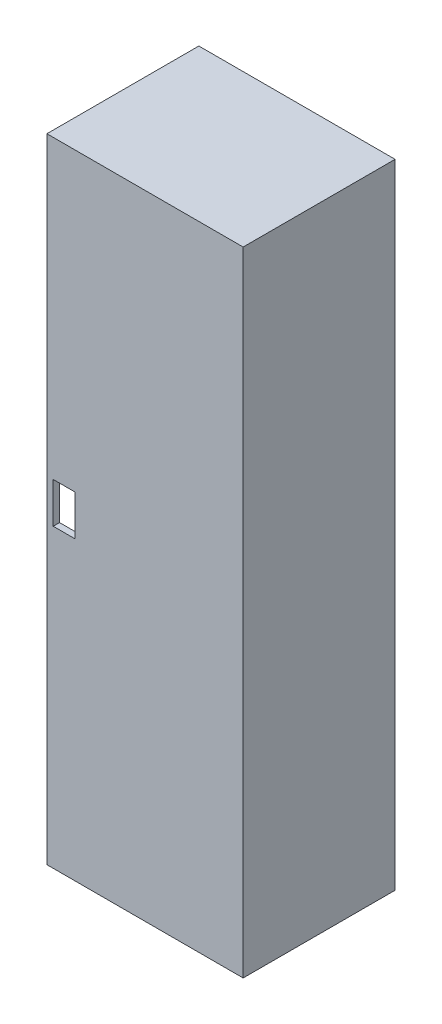
SolidWorks part; units mm, degrees
material "PLA"
ref_plane "Front Plane" through (0, 0, 0) normal (1, 0, 0) x (0, 1, 0)
ref_plane "Top Plane" through (0, 0, 0) normal (0, 0, 1) x (0, 1, 0)
ref_plane "Right Plane" through (0, 0, 0) normal (0, 1, 0) x (-1, 0, 0)
sketch "Sketch1" plane through (0, 0, 0) normal (0, 0, 1) x (0, 1, 0)
  line L1 (-125, -40) -> (125, -40)
  line L2 (-125, -40) -> (-125, 40)
  line L3 (-125, 40) -> (125, 40)
  line L4 (125, -40) -> (125, 40)
  line L5 (-125, -40) -> (125, 40) construction
  line L6 (-125, 40) -> (125, -40) construction
  point P0 (0, 0)
  dimension "D1" = 250
extrude "Boss-Extrude1" add sketch "Sketch1" along normal blind 2.5
sketch "Sketch2" plane through (0, 0, 0) normal (0, 0, -1) x (1, 0, 0)
  line L1 (-40, 125) -> (40, 125) construction
  line L2 (-37.5, -122.5) -> (37.5, -122.5)
  line L3 (-37.5, -122.5) -> (-37.5, 122.5)
  line L4 (-40, -125) -> (40, -125)
  line L5 (40, -125) -> (40, 125)
  line L6 (40, 125) -> (-40, 125)
  line L7 (-40, 125) -> (-40, -125)
  line L8 (-40, -125) -> (40, -125)
  line L9 (40, -125) -> (40, 125)
  line L10 (40, 125) -> (-40, 125)
  line L11 (-40, 125) -> (-40, -125)
  line L12 (-37.5, 122.5) -> (37.5, 122.5)
  line L13 (37.5, -122.5) -> (37.5, 122.5)
  line L14 (-37.5, -122.5) -> (37.5, 122.5) construction
  line L15 (-37.5, 122.5) -> (37.5, -122.5) construction
  point P2 (0, 0)
  dimension "D2" = 2.5
  dimension "D3" = 2.5
extrude "Boss-Extrude2" add sketch "Sketch2" along normal blind 55
sketch "Sketch3" plane through (0, 0, -55) normal (0, 0, -1) x (1, 0, 0)
  line L1 (40, 125) -> (-40, 125)
  line L2 (40, 125) -> (40, -125)
  line L3 (40, -125) -> (-40, -125)
  line L4 (-40, 125) -> (-40, -125)
extrude "Boss-Extrude3" add sketch "Sketch3" along normal blind 2.5
sketch "Sketch4" plane through (-40, 0, 0) normal (-1, 0, 0) x (0, -1, 0)
  line L5 (-125, 2.5) -> (125, 2.5)
  line L6 (-125, 2.5) -> (-125, -57.5)
  line L7 (-125, -57.5) -> (125, -57.5)
  line L8 (125, 2.5) -> (125, -57.5)
extrude "Cut-Extrude1" cut sketch "Sketch4" against normal blind 2.5
sketch "Sketch5" plane through (0, 0, 2.5) normal (0, 0, 1) x (1, 0, 0)
  line L0 (-26.5, 0) -> (-35, 0) construction
  line L1 (-35, 8) -> (-26.5, 8)
  line L2 (-35, 8) -> (-35, -8)
  line L3 (-35, -8) -> (-26.5, -8)
  line L4 (-26.5, 8) -> (-26.5, -8)
  line L6 (0, 0) -> (-37.5, 0) construction
  line L7 (-37.5, -125) -> (-37.5, 125) construction
  dimension "D3" = 2.5
  dimension "D1" = 16
  dimension "D2" = 8.5
extrude "Cut-Extrude2" cut sketch "Sketch5" against normal up to next
sketch "Sketch7" plane through (0, 0, -55) normal (0, 0, 1) x (1, 0, 0)
  line L0 (24.35, 17.1) -> (-5.65, 17.1) construction
  line L1 (-5.65, 12.9) -> (24.35, 12.9) construction
  line L2 (24.35, 17.1) -> (-5.65, 17.1) construction
  line L3 (-5.65, 12.9) -> (24.35, 12.9) construction
  line L4 (-37.5, -122.5) -> (37.5, -122.5)
  line L5 (37.5, -122.5) -> (37.5, 122.5)
  line L6 (37.5, 122.5) -> (-37.5, 122.5)
  line L7 (-37.5, 122.5) -> (-37.5, -122.5)
  line L8 (-37.5, -122.5) -> (37.5, -122.5)
  line L9 (37.5, -122.5) -> (37.5, 122.5)
  line L10 (37.5, 122.5) -> (-37.5, 122.5)
  line L11 (-37.5, 122.5) -> (-37.5, -122.5)
  line L12 (26.45, 15) -> (-7.75, 15) construction
  arc A0 (24.35, 12.9) -> (26.45, 15) centre (24.35, 15) ccw construction
  arc A1 (24.35, 12.9) -> (26.45, 15) centre (24.35, 15) ccw construction
  arc A2 (26.45, 15) -> (24.35, 17.1) centre (24.35, 15) ccw construction
  arc A3 (-7.75, 15) -> (-5.65, 12.9) centre (-5.65, 15) ccw construction
  arc A4 (-5.65, 17.1) -> (-7.75, 15) centre (-5.65, 15) ccw construction
  arc A5 (26.45, 15) -> (24.35, 17.1) centre (24.35, 15) ccw construction
  arc A6 (-7.75, 15) -> (-5.65, 12.9) centre (-5.65, 15) ccw construction
  arc A7 (-5.65, 17.1) -> (-7.75, 15) centre (-5.65, 15) ccw construction
  point P12 (21.45, 15)
  point P13 (-2.75, 15)
  dimension "D2" = 5
  dimension "D3" = 5
  dimension "D1" = 0
hole_wizard "M4 Clearance Hole1" positions "Sketch7" profile "Sketch11" hole size "M4" standard "ANSI Metric" end condition through all
sketch "Sketch11" plane through (-2.75, 15, -55) normal (1, 0, 0) x (0, -1, 0)
  line L0 (0, 0) -> (0, 2.5)
  line L1 (0, 2.5) -> (2.25, 2.5)
  line L2 (2.25, 2.5) -> (2.25, 0)
  line L5 (2.25, 0) -> (0, 0)
  line L11 (0, -6.35) -> (0, 107.95) construction
  dimension "Thru Hole Dia." = 4.5
  dimension "Thru Hole Depth" = 2.5
mirror "Mirror1" about plane through (0, 0, 0) normal (0, 1, 0) of "M4 Clearance Hole1"
equation "\"ball_diameter\"= 0.75in"
equation "\"wall_thickness\" = 0.25cm"
equation "\"track_length\" = 25cm"
equation "\"axle\" = 5mm"
equation "\"D1@Sketch1\"=\"track_length\""
equation "\"D1@Boss-Extrude1\"=\"wall_thickness\""
equation "\"D2@Sketch2\"=\"wall_thickness\""
equation "\"D3@Sketch2\"=\"wall_thickness\""
equation "\"D1@Boss-Extrude3\"=\"wall_thickness\""
equation "\"D3@Sketch5\"=\"wall_thickness\""
